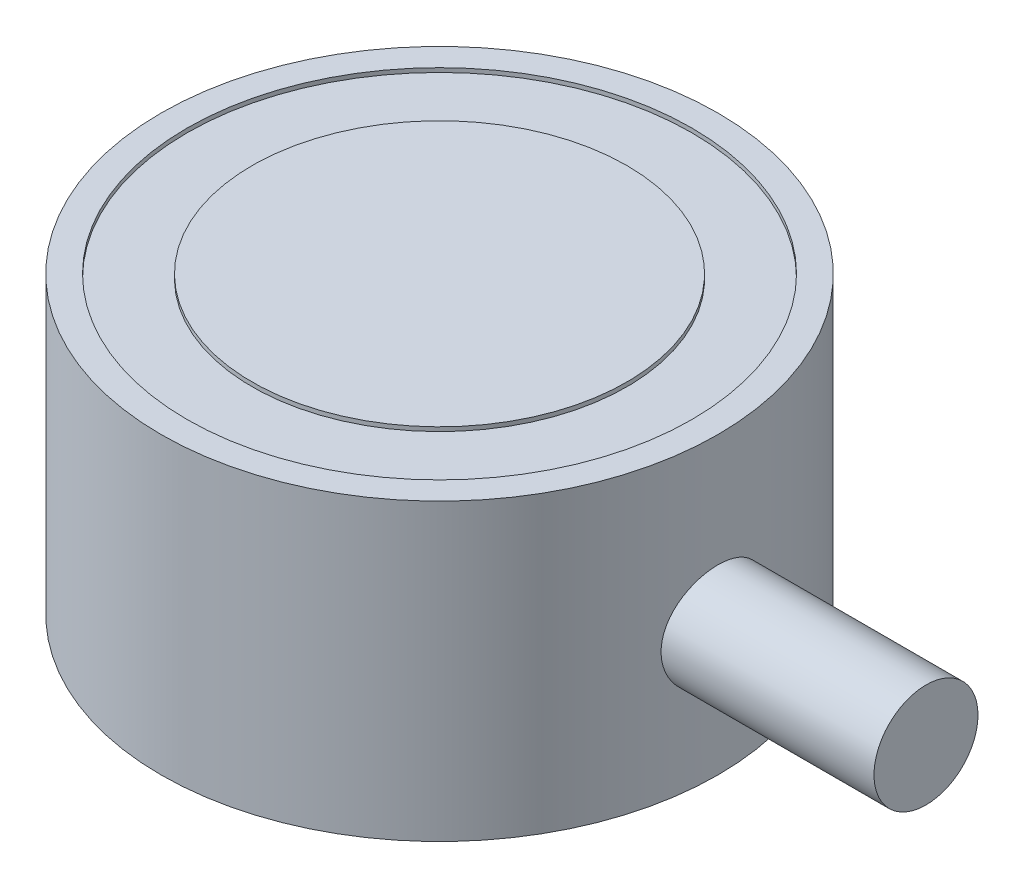
SolidWorks part; units mm, degrees
ref_plane "Front Plane" through (0, 0, 0) normal (0, 0, 1) x (1, 0, 0)
ref_plane "Top Plane" through (0, 0, 0) normal (0, 1, 0) x (1, 0, 0)
ref_plane "Right Plane" through (0, 0, 0) normal (1, 0, 0) x (0, 0, -1)
sketch "Sketch1" plane through (0, 0, 0) normal (0, 1, 0) x (1, 0, 0)
  circle A0 centre (0, 0) radius 17
  dimension "A" = 34
extrude "Boss-Extrude1" add sketch "Sketch1" along normal blind 18
sketch "Sketch2" plane through (0, 0, 0) normal (0, 0, 1) x (1, 0, 0)
  line L0 (-15.4125, 18) -> (-15.4125, 17.746)
  line L1 (-15.4125, 17.746) -> (-11.4438, 17.746)
  line L2 (-11.4438, 17.746) -> (-11.4438, 18)
  line L3 (17, 18) -> (-17, 18) construction
  line L4 (-11.4438, 18) -> (-15.4125, 18)
  line L5 (0, 0) -> (0, 18) construction
  line L6 (-17, 18) -> (-17, 0) construction
  dimension "D1" = 1.5875
  dimension "D2" = 3.9688
  dimension "D3" = 0.254
revolve "Cut-Revolve1" cut sketch "Sketch2" angle 360 about L5
sketch "Sketch3" plane through (0, 0, 0) normal (0, -1, 0) x (1, 0, 0)
  circle A0 centre (0, 0) radius 2.413
  point P3 (-2.413, 0)
  point P4 (2.413, 0)
  point P5 (0, 0)
  dimension "Hole Dia." = 4.826
extrude "Cut-Extrude1" cut sketch "Sketch3" against normal blind 9.525
sketch "Sketch4" plane through (0, 0, 0) normal (0, -1, 0) x (1, 0, 0)
  circle A1 centre (0, 0) radius 2.413
  circle A2 centre (0, 0) radius 2.413
  point P0 (-2.413, 0)
  dimension "D1" = 0
curve "Helix/Spiral1" pitch 0.7937 height 10.3188 turns 13 parameters "Pitch"=0.7937
sketch "Sketch5" plane through (0, 0, 0) normal (0, 0, 1) x (1, 0, 0)
  line L0 (-2.4989, 0.0496) -> (-2.4989, -0.7441) construction
  line L1 (-2.4989, -0.7441) -> (-1.8115, -0.3473) construction
  line L2 (-1.8115, -0.3473) -> (-2.4989, 0.0496) construction
  line L3 (-2.413, 0) -> (-2.413, -0.6945) construction
  line L4 (-1.8974, -0.2977) -> (-1.8974, -0.3969) construction
  line L5 (-1.8115, -0.3473) -> (-1.8974, -0.3473) construction
  line L6 (-1.8974, -0.3473) -> (-1.9834, -0.3473) construction
  line L7 (-2.413, -0.3473) -> (-2.4989, -0.3473) construction
  line L8 (-2.456, -0.7193) -> (-2.456, 0.0248)
  line L9 (-2.456, 0.0248) -> (-1.9834, -0.248)
  line L10 (-1.9834, -0.248) -> (-1.9834, -0.4465)
  line L11 (-1.9834, -0.4465) -> (-2.456, -0.7193)
  point P16 (-2.456, -0.3473)
  dimension "D1" = 0.7937
  dimension "D2" = 0.0992
sketch "Sketch6" plane through (0, 0, 0) normal (0, -1, 0) x (1, 0, 0)
  circle A0 centre (0, 0) radius 2.4989
sweep "Sweep1" add profiles "Sketch5" path "Helix/Spiral1"
extrude "Cut-Extrude2" cut sketch "Sketch6" against normal through all draft 45 and the other way through all
sketch "Sketch7" plane through (0, 0, 0) normal (1, 0, 0) x (0, 0, -1)
  line L0 (0, 7.9375) -> (0, 0) construction
  circle A0 centre (0, 7.9375) radius 3.175
  dimension "Wire Dia." = 6.35
  dimension "G" = 4.7625
sketch "Sketch8" plane through (0, 0, 0) normal (0, 0, 1) x (1, 0, 0)
  line L0 (0, 7.9375) -> (29.7, 7.9375) construction
  line L1 (17, 0) -> (17, 18) construction
  dimension "D1" = 12.7
extrude "Boss-Extrude2" add sketch "Sketch7" against normal up to surface (12.9991 mm away) from vertex at 29.7 starting at point (29.7, 7.9375, 0)
sketch "Sketch9" plane through (0, 0, 0) normal (0, 0, 1) x (1, 0, 0)
  line L0 (-2.413, 0) -> (-2.413, 9.525) construction
  line L1 (-2.413, 9.525) -> (2.413, 9.525) construction
  line L2 (2.413, 9.525) -> (2.413, 0) construction
  line L3 (-2.413, 9.525) -> (0.759, 9.525) construction
equation "\"D3@Helix/Spiral1\" = \"Pitch@Helix/Spiral1\" + \"Hole Depth@Cut-Extrude1\""
equation "\"D1@Sketch5\" = \"Pitch@Helix/Spiral1\""
equation "\"D2@Sketch5\" = \"D1@Sketch5\" / 8"
